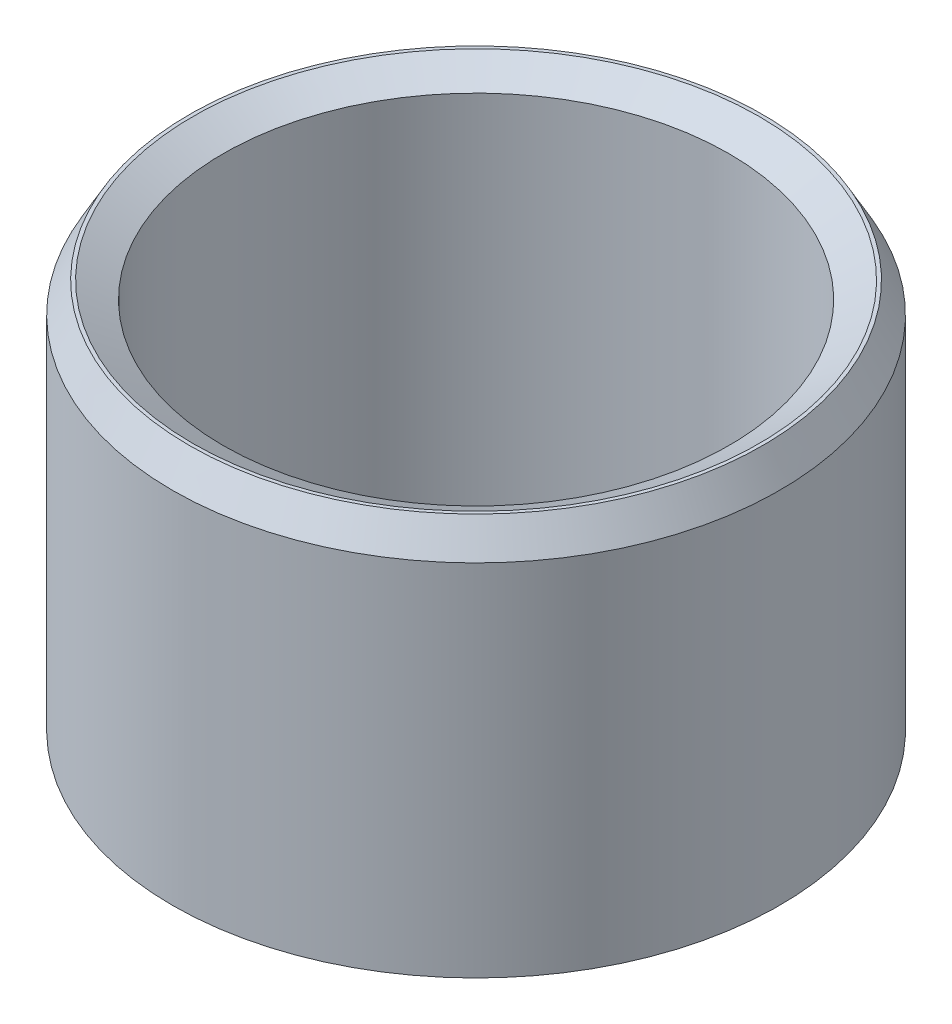
SolidWorks part; units mm, degrees
ref_plane "Front Plane" through (0, 0, 0) normal (0, 0, 1) x (1, 0, 0)
ref_plane "Top Plane" through (0, 0, 0) normal (0, 1, 0) x (1, 0, 0)
ref_plane "Right Plane" through (0, 0, 0) normal (1, 0, 0) x (0, 0, -1)
sketch "Sketch1" plane through (0, 0, 0) normal (0, 1, 0) x (1, 0, 0)
  circle A0 centre (0, 0) radius 37.5
  dimension "SLEEVE_OD" = 75
extrude "Boss-Extrude1" add sketch "Sketch1" along normal blind 50.2277
sketch "Sketch2" plane through (0, 0, 0) normal (0, 1, 0) x (1, 0, 0)
  circle A0 centre (0, 0) radius 31.2305
  dimension "BORE_D" = 62.4611
extrude "Cut-Extrude1" cut sketch "Sketch2" along normal through all
chamfer "Chamfer1" distance 3.7433 angle 29.212 4 edges at (0, 50.2277, 31.2305) (0, 0, 31.2305) (0, 0, 37.5) (0, 50.2277, 37.5) first distance on face at (0, 50.2277, 31.2305) first distance on face at (0, 0, 31.2305) first distance on face at (0, 50.2277, 37.5)
